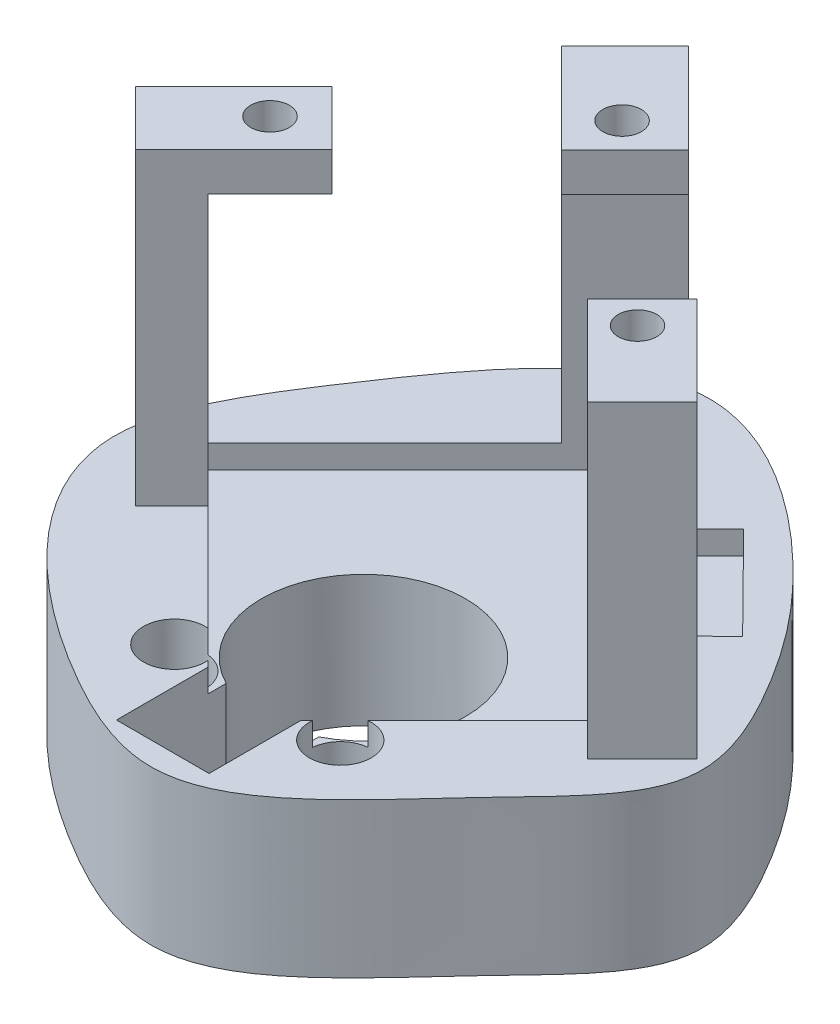
SolidWorks part; units mm, degrees
ref_plane "Front Plane" through (0, 0, 0) normal (0, 0, 1) x (1, 0, 0)
ref_plane "Top Plane" through (0, 0, 0) normal (0, 1, 0) x (1, 0, 0)
ref_plane "Right Plane" through (0, 0, 0) normal (1, 0, 0) x (0, 0, -1)
sketch "Sketch2" plane through (0, 0, 0) normal (0, 1, 0) x (1, 0, 0)
  circle A0 centre (0, 0) radius 60
extrude "Boss-Extrude1" add sketch "Sketch2" along normal blind 10 and the other way blind 10 contours A0
sketch "Sketch4" plane through (0, 10, 0) normal (0, 1, 0) x (1, 0, 0)
  circle A1 centre (0, 6) radius 13.225
sketch "Sketch6" plane through (0, 10, 0) normal (0, 1, 0) x (1, 0, 0)
  line L0 (-5.9779, 23.0428) -> (5.9779, 10.9572)
  line L1 (-5.9779, 23.0428) -> (13.2168, 42.0313)
  line L2 (5.9779, 10.9572) -> (25.1725, 29.9458)
  line L3 (13.2168, 42.0313) -> (25.1725, 29.9458)
  point P2 (15.5752, 20.4515)
  point P5 (3.6195, 32.537)
  dimension "D1" = 17
  dimension "D2" = 27
sketch "Sketch7" plane through (0, 10, 0) normal (0, 1, 0) x (1, 0, 0)
  circle A0 centre (-10.75, -7.75) radius 4
  dimension "D1" = 8
extrude "Cut-Extrude2" cut sketch "Sketch7" against normal blind 15 contours A0
mirror "Mirror1" about plane through (0, 0, 0) normal (1, 0, 0) of "Cut-Extrude2"
sketch "Sketch9" plane through (0, 10, 0) normal (0, 1, 0) x (1, 0, 0)
  line L0 (-31.1127, 17) -> (0, 48.1127)
  line L1 (-31.1127, 17) -> (0, -14.1127)
  line L2 (0, 48.1127) -> (31.1127, 17)
  line L3 (0, -14.1127) -> (31.1127, 17)
  dimension "D1" = 44
  dimension "D2" = 44
extrude "Cut-Extrude4" cut sketch "Sketch9" against normal blind 3
extrude "Cut-Extrude5" cut sketch "Sketch6" against normal blind 3
sketch "Sketch11" plane through (0, 10, 0) normal (0, 1, 0) x (1, 0, 0)
  line L0 (0, 48.1127) -> (-8.24, 39.8727)
  line L1 (0, 48.1127) -> (-4.5593, 52.672)
  line L2 (-8.24, 39.8727) -> (-12.7993, 44.432)
  line L3 (-4.5593, 52.672) -> (-12.7993, 44.432)
  line L4 (-31.1127, 17) -> (-24.0416, 9.9289)
  line L5 (-31.1127, 17) -> (-35.8263, 12.2864)
  line L6 (-24.0416, 9.9289) -> (-28.7552, 5.2154)
  line L7 (-35.8263, 12.2864) -> (-28.7552, 5.2154)
  line L8 (-31.1127, 17) -> (-10.3418, -3.7709) construction
  line L9 (31.6446, 17.5319) -> (24.5735, 10.4608)
  line L10 (31.6446, 17.5319) -> (35.9355, 13.241)
  line L11 (24.5735, 10.4608) -> (28.8645, 6.1699)
  line L12 (35.9355, 13.241) -> (28.8645, 6.1699)
  line L13 (10.3418, -3.7709) -> (31.1127, 17) construction
  line L14 (0, 48.1127) -> (-31.1127, 17) construction
  dimension "D1" = 11.6531
  dimension "D2" = 10
  dimension "D3" = 10
extrude "Boss-Extrude2" add sketch "Sketch11" along normal blind 35
sketch "Sketch12" plane through (0, 45, 0) normal (0, 1, 0) x (1, 0, 0)
  line L0 (-4.5593, 52.672) -> (-12.7993, 44.432)
  line L1 (-4.5593, 52.672) -> (7.108, 41.0047)
  line L2 (-12.7993, 44.432) -> (-1.132, 32.7647)
  line L3 (7.108, 41.0047) -> (-1.132, 32.7647)
  line L4 (-35.8263, 12.2864) -> (-28.7552, 5.2154)
  line L5 (-35.8263, 12.2864) -> (-23.0984, 25.0143)
  line L6 (-28.7552, 5.2154) -> (-16.0273, 17.9433)
  line L7 (-23.0984, 25.0143) -> (-16.0273, 17.9433)
  line L8 (35.9355, 13.241) -> (28.8645, 6.1699)
  line L9 (35.9355, 13.241) -> (24.3378, 24.8387)
  line L10 (28.8645, 6.1699) -> (17.2667, 17.7677)
  line L11 (24.3378, 24.8387) -> (17.2667, 17.7677)
extrude "Boss-Extrude3" add sketch "Sketch12" along normal blind 5
sketch "Sketch13" plane through (0, 50, 0) normal (0, 1, 0) x (1, 0, 0)
  circle A0 centre (-0.5, 40) radius 2.5
  dimension "D1" = 5
sketch "Sketch14" plane through (0, 50, 0) normal (0, 1, 0) x (1, 0, 0)
  circle A0 centre (23.5, 18) radius 2.5
sketch "Sketch15" plane through (0, 50, 0) normal (0, 1, 0) x (1, 0, 0)
  circle A0 centre (-23.777, 17.669) radius 2.5
extrude "Cut-Extrude7" cut sketch "Sketch13" against normal blind 5 contours A0
extrude "Cut-Extrude8" cut sketch "Sketch15" against normal blind 5 contours A0
extrude "Cut-Extrude9" cut sketch "Sketch14" against normal blind 5 contours A0
sketch "Sketch16" plane through (0, 10, 0) normal (0, 1, 0) x (1, 0, 0)
  spline S0 degree 3 poles (-27.5345, 35.3123) (-7.4919, 63.2621) (20.1768, 43.1639) (32.0959, 27.7397) (41.1035, 9.3847) (23.4414, -7.0123) (7.3872, -27.6695) (-20.6756, -15.2656) (-45.2159, 6.8631) (-27.5345, 35.3123) (-7.4919, 63.2621) (20.1768, 43.1639) knots -0.41993 -0.246246 -0.147029 0 0.129983 0.21607 0.283536 0.368924 0.507401 0.58007 0.753754 0.852971 1 1.129983 1.21607 1.283536 only from (-4.7945, 54.4115) to (-4.7945, 54.4115)
  circle M1 centre (0, 0) radius 60
extrude "Cut-Extrude10" cut sketch "Sketch16" against normal blind 38 contours S0 M1 | S0 region at (-58.3029, 10, 0)
extrude "Cut-Extrude12" cut sketch "Sketch4" against normal blind 42 contours A1
sketch "Sketch19" plane through (0, 10, 0) normal (0, 1, 0) x (1, 0, 0)
  line L0 (-6, 0) -> (-6, -20)
  line L1 (-6, 0) -> (6, 0)
  line L2 (-6, -20) -> (6, -20)
  line L3 (6, 0) -> (6, -20)
extrude "Cut-Extrude13" cut sketch "Sketch19" against normal blind 17
